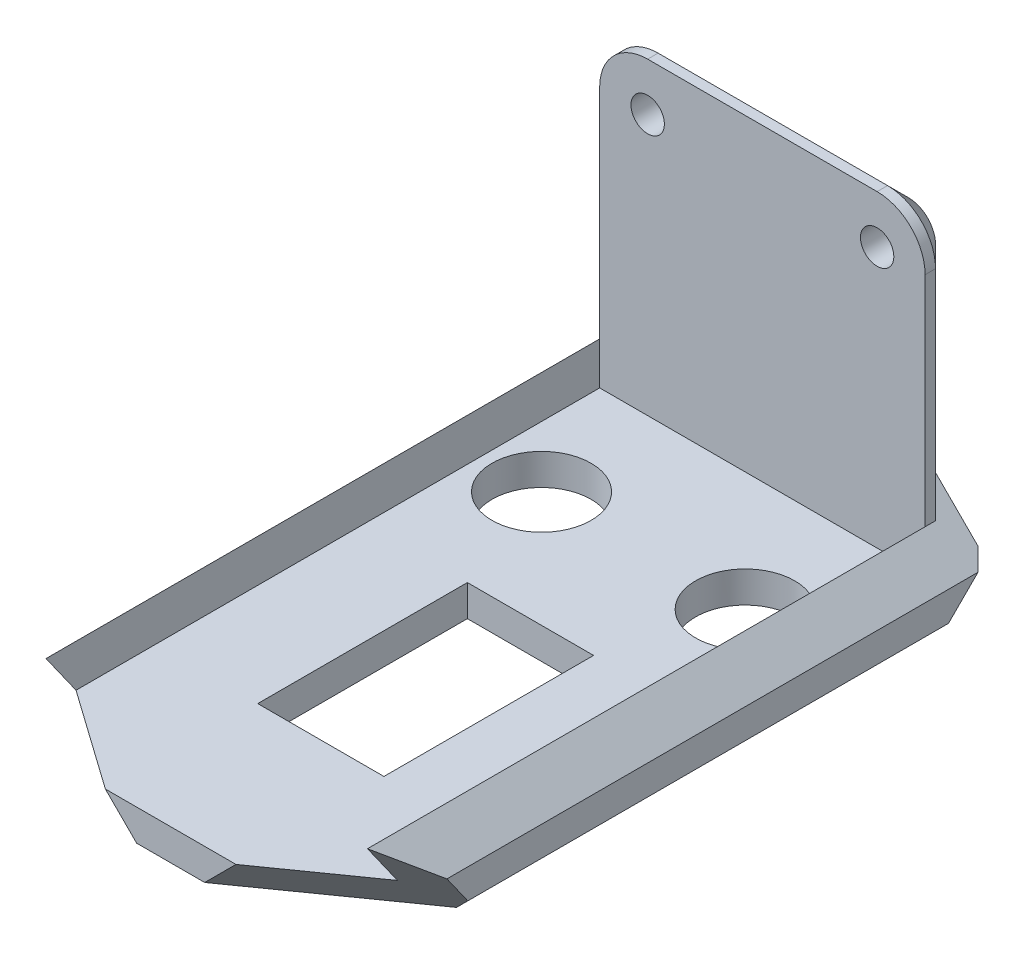
SolidWorks part; units mm, degrees
ref_plane "Front Plane" through (0, 0, 0) normal (0, 0, 1) x (1, 0, 0)
ref_plane "Top Plane" through (0, 0, 0) normal (0, 1, 0) x (1, 0, 0)
ref_plane "Right Plane" through (0, 0, 0) normal (1, 0, 0) x (0, 0, -1)
sketch "Sketch1" plane through (0, 0, 0) normal (0, 0, 1) x (1, 0, 0)
  line L0 (-11, 0) -> (11, 0)
  line L1 (-11, 4.6) -> (11, 4.6)
  line L2 (-15.6, 0) -> (-15.6, -25)
  line L3 (15.6, 0) -> (15.6, -25)
  line L4 (-15.6, -25) -> (15.6, -25)
  circle A0 centre (-11, 0) radius 1.6
  circle A1 centre (11, 0) radius 1.6
  circle A2 centre (-11, 0) radius 4.6
  circle A3 centre (11, 0) radius 4.6
  point P4 (0, 0)
  dimension "D2" = 3.2
  dimension "D3" = 3.2
  dimension "D5" = 25
  dimension "D1" = 22
  dimension "D6" = 25
  dimension "D4" = 3
extrude "Boss-Extrude1" add sketch "Sketch1" along normal blind 3
sketch "Sketch3" plane through (0, 0, 0) normal (0, 0, -1) x (-1, 0, 0)
  line L1 (15.6, -25) -> (-15.6, -25)
  line L2 (15.6, -25) -> (15.6, -28)
  line L3 (15.6, -28) -> (-15.6, -28)
  line L4 (11, 4.6) -> (-11, 4.6)
  line L5 (-15.6, 0) -> (-15.6, -25)
  line L6 (-15.6, -25) -> (15.6, -25)
  line L7 (15.6, -25) -> (15.6, 0)
  line L8 (11, 4.6) -> (-11, 4.6)
  line L9 (-15.6, 0) -> (-15.6, -25)
  line L10 (-15.6, -25) -> (15.6, -25)
  line L11 (15.6, -25) -> (15.6, 0)
  line L12 (-15.6, -25) -> (-15.6, -28)
  arc A2 (-11, 4.6) -> (-15.6, 0) centre (-11, 0) ccw
  arc A3 (15.6, 0) -> (11, 4.6) centre (11, 0) ccw
  arc A4 (-11, 4.6) -> (-15.6, 0) centre (-11, 0) ccw
  arc A5 (15.6, 0) -> (11, 4.6) centre (11, 0) ccw
  line M11 (-15.6, -25) -> (15.6, -25)
  dimension "D2" = 3
  dimension "D1" = 0
extrude "Boss-Extrude2" add sketch "Sketch3" against normal blind 60 contours L12 L3 L2 M11
sketch "Sketch4" plane through (0, 0, 0) normal (0, 0, -1) x (-1, 0, 0)
  line L0 (-15.6, -20.9289) -> (-22.6711, -28)
  line L1 (-22.6711, -28) -> (-15.6, -28)
  line L2 (0, 0) -> (0, -4.6682) construction
  line L3 (22.6711, -28) -> (15.6, -28)
  line L4 (11, 4.6) -> (-11, 4.6)
  line L5 (-15.6, 0) -> (-15.6, -28)
  line L6 (-15.6, -28) -> (15.6, -28)
  line L7 (15.6, -28) -> (15.6, 0)
  line L8 (11, 4.6) -> (-11, 4.6)
  line L9 (-15.6, 0) -> (-15.6, -28)
  line L10 (-15.6, -28) -> (15.6, -28)
  line L11 (15.6, -28) -> (15.6, 0)
  line L12 (15.6, -20.9289) -> (22.6711, -28)
  arc A2 (-11, 4.6) -> (-15.6, 0) centre (-11, 0) ccw
  arc A3 (15.6, 0) -> (11, 4.6) centre (11, 0) ccw
  arc A4 (-11, 4.6) -> (-15.6, 0) centre (-11, 0) ccw
  arc A5 (15.6, 0) -> (11, 4.6) centre (11, 0) ccw
  line M12 (-15.6, 0) -> (-15.6, -28)
  line M14 (15.6, -28) -> (15.6, 0)
  dimension "D2" = 10
  dimension "D3" = 45
  dimension "D1" = 0
extrude "Boss-Extrude3" add sketch "Sketch4" against normal up to surface (60 mm away) contours L0 L1 M12 | L12 L3 M14 up to face at (0, -26.5, 60)
chamfer "Chamfer1" distance 5 angle 45 3 edges at (0, -28, 0) (22.6711, -28, 30) (-22.6711, -28, 30)
chamfer "Chamfer2" distance 2 angle 45 5 edges at (-15.6, -10.4645, 0) (-14.2527, 3.2527, 0) (0, 4.6, 0) (14.2527, 3.2527, 0) (15.6, -10.4645, 0)
chamfer "Chamfer3" distance 2 angle 45 1 edges at (-19.1355, -28, 32.5)
chamfer "Chamfer4" distance 2 angle 45 1 edges at (20.1711, -25.5, 31.25)
sketch "Sketch5" plane through (0, -28, 0) normal (0, -1, 0) x (1, 0, 0)
  line L0 (17.6711, 35.5531) -> (-17.1355, 35.5531) construction
  line L2 (6.3178, 45.6031) -> (-5.7822, 45.6031)
  line L3 (6.3178, 45.6031) -> (6.3178, 25.5031)
  line L4 (17.6711, 60) -> (-17.1355, 60)
  line L5 (-17.1355, 60) -> (-17.1355, 5)
  line L6 (-17.1355, 5) -> (17.6711, 5)
  line L7 (17.6711, 5) -> (17.6711, 60)
  line L8 (17.6711, 60) -> (-17.1355, 60)
  line L9 (-17.1355, 60) -> (-17.1355, 5)
  line L10 (-17.1355, 5) -> (17.6711, 5)
  line L11 (17.6711, 5) -> (17.6711, 60)
  line L12 (6.3178, 25.5031) -> (-5.7822, 25.5031)
  line L13 (-5.7822, 45.6031) -> (-5.7822, 25.5031)
  line L14 (6.3178, 45.6031) -> (-5.7822, 25.5031) construction
  line L15 (6.3178, 25.5031) -> (-5.7822, 45.6031) construction
  point P6 (0.2678, 35.5531)
  dimension "D2" = 20.1
  dimension "D3" = 12.1
  dimension "D1" = 0
extrude "Cut-Extrude1" cut sketch "Sketch5" against normal blind 30 contours L3 L2 L13 L12
sketch "Sketch6" plane through (0, -28, 0) normal (0, -1, 0) x (1, 0, 0)
  line L0 (0, 0) -> (0, 10.9602) construction
  line L1 (17.6711, 0) -> (-17.6711, 0) construction
  circle A0 centre (9.7612, 14.4137) radius 4.75
  circle A1 centre (-9.7612, 14.4137) radius 4.75
  dimension "D1" = 9.5
extrude "Cut-Extrude2" cut sketch "Sketch6" against normal blind 30
chamfer "Chamfer5" distance 10 angle 45 2 edges at (-18.1355, -27, 60) (18.214, -27.4571, 60)
